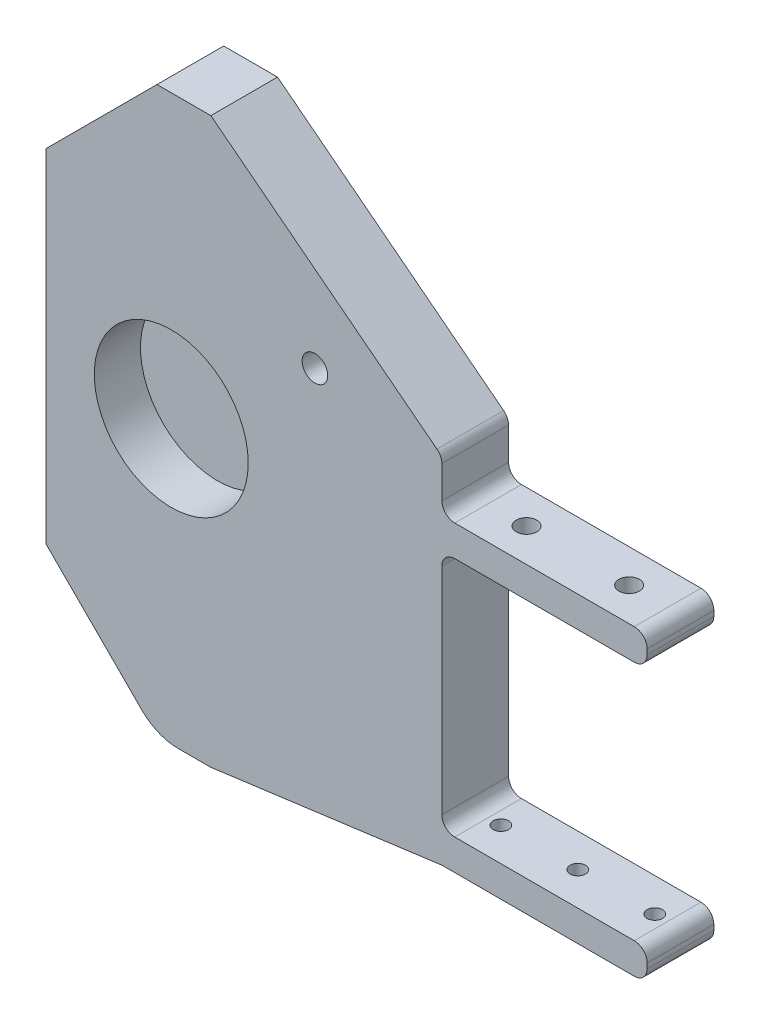
SolidWorks part; units mm, degrees
material "5052-H36"
ref_plane "Plano frontal" through (0, 0, 0) normal (0, 0, 1) x (1, 0, 0)
ref_plane "Plano superior" through (0, 0, 0) normal (0, 1, 0) x (1, 0, 0)
ref_plane "Plano direito" through (0, 0, 0) normal (1, 0, 0) x (0, 0, -1)
sketch "Esboço1" plane through (0, 0, 0) normal (0, 0, 1) x (1, 0, 0)
  line L0 (79.1281, 0) -> (0, 0) construction
  line L3 (4.9801, 55) -> (32.742, 55)
  line L6 (32.742, 55) -> (-22.7817, 55)
  line L12 (-22.7817, 55) -> (-44.3754, 33.4063)
  line L14 (-44.3754, -33.4063) -> (-22.7817, -55)
  line L15 (-22.7817, -55) -> (32.742, -55)
  line L18 (393.8557, 316.0739) -> (396.402, 318.6203) [skipped]
  line L19 (55, 501.996) -> (55, 520.8093) [skipped]
  line L20 (-316.0739, 393.8557) -> (-318.6203, 396.402) [skipped]
  line L21 (32.742, 55) -> (32.742, 10)
  line L22 (32.742, -49) -> (32.742, -55)
  line L23 (32.742, -49) -> (72.742, -49)
  line L25 (32.742, -43) -> (72.742, -43)
  line L26 (72.742, -49) -> (72.742, -43)
  line L27 (32.742, 4) -> (32.742, -43)
  line L28 (32.742, 4) -> (72.742, 4)
  line L30 (32.742, 10) -> (72.742, 10)
  line L31 (72.742, 4) -> (72.742, 10)
  line L32 (-44.3754, 33.4063) -> (-44.3754, -33.4063)
  line L34 (-55, 7.7563) -> (-55, -6.3461) [skipped]
  circle A0 centre (0, 0) radius 15 construction
  arc A3 (4.9801, 55) -> (0, -55.225) centre (0, 0) ccw construction
  point P14 (4.9801, 55)
  dimension "D1" = 30
  dimension "D5" = 110
  dimension "D6" = 40
  dimension "D7" = 6
  dimension "D8" = 6
  dimension "D9" = 45
extrude "Ressalto-extrusão1" add sketch "Esboço1" along normal mid plane 13 contours L14 L15 L3 L6 L12 A0 region at (-0.7875, -1.1016, 0)
sketch "Esboço2" plane through (0, 0, 6.5) normal (0, 0, 1) x (1, 0, 0)
  circle A1 centre (-20, 0) radius 15
  dimension "D1" = 30
  dimension "D2" = 20
extrude "Corte-extrusão1" cut sketch "Esboço2" against normal blind 9
sketch "Esboço3" plane through (0, 0, 6.5) normal (0, 0, 1) x (1, 0, 0)
  line L0 (-22.7817, -55) -> (32.742, -55) construction
  line L1 (-12.2817, -55) -> (32.742, -49)
  line L2 (32.742, -49) -> (32.742, -55)
  line L3 (32.742, -55) -> (-12.2817, -55)
  line L4 (-12.2817, -55) -> (-12.2817, 66.3095) construction
  line L6 (32.742, 10) -> (72.742, 10) construction
  line L11 (32.742, 55) -> (-12.2817, 55)
  line L12 (-12.2817, 55) -> (32.742, 20)
  line L13 (32.742, 20) -> (32.742, 55)
  circle A0 centre (8, 22.5) radius 2.5
  point P0 (-12.2817, -55)
  dimension "D2" = 5
  dimension "D1" = 10.5
  dimension "D3" = 22.5
  dimension "D4" = 28
  dimension "D5" = 10
extrude "Corte-extrusão2" cut sketch "Esboço3" against normal blind 13
fillet "Filete1" radius 10 1 edges at (-22.7817, -55, 0)
sketch "Esboço4" plane through (0, 0, -6.5) normal (0, 0, -1) x (-1, 0, 0)
  line L0 (44.3754, 33.4063) -> (44.3754, -33.4063) construction
  circle A0 centre (36.3754, 8.4063) radius 2
  circle A1 centre (12.9554, -16.5937) radius 2
  circle A2 centre (22.3754, -27.5937) radius 2
  dimension "D1" = 4
  dimension "D2" = 25
  dimension "D3" = 8
  dimension "D4" = 23.42
  dimension "D5" = 25
  dimension "D6" = 36
  dimension "D7" = 14
extrude "Corte-extrusão3" cut sketch "Esboço4" against normal blind 10
sketch "Esboço6" plane through (0, 10, 0) normal (0, 1, 0) x (1, 0, 0)
  circle A0 centre (42.742, -0.0016) radius 2
  circle A1 centre (62.742, -0.0016) radius 2
  circle A2 centre (42.742, -0.0016) radius 2 construction
  dimension "D1" = 20
extrude "Corte-extrusão4" cut sketch "Esboço6" against normal blind 10
sketch "Esboço7" plane through (0, -49, 0) normal (0, -1, 0) x (1, 0, 0)
  line L0 (32.742, -6.5) -> (72.742, -6.5) construction
  line L1 (37.742, 0) -> (67.742, 0) construction
  line L2 (72.742, 6.5) -> (72.742, -6.5) construction
  circle A0 centre (37.742, 0) radius 1.5
  circle A1 centre (52.742, 0) radius 1.5
  circle A2 centre (67.742, 0) radius 1.5
  dimension "D1" = 3
  dimension "D2" = 6.5
  dimension "D3" = 5
  dimension "D4" = 20
  dimension "D5" = 35
extrude "Corte-extrusão5" cut sketch "Esboço7" against normal blind 10
fillet "Filete2" radius 2.5 8 edges at (72.742, -49, 0) (72.742, -43, 0) (72.742, 4, 0) (72.742, 10, 0) (32.742, 20, 0) (32.742, -43, 0) (32.742, 10, 0) (32.742, 4, 0)
